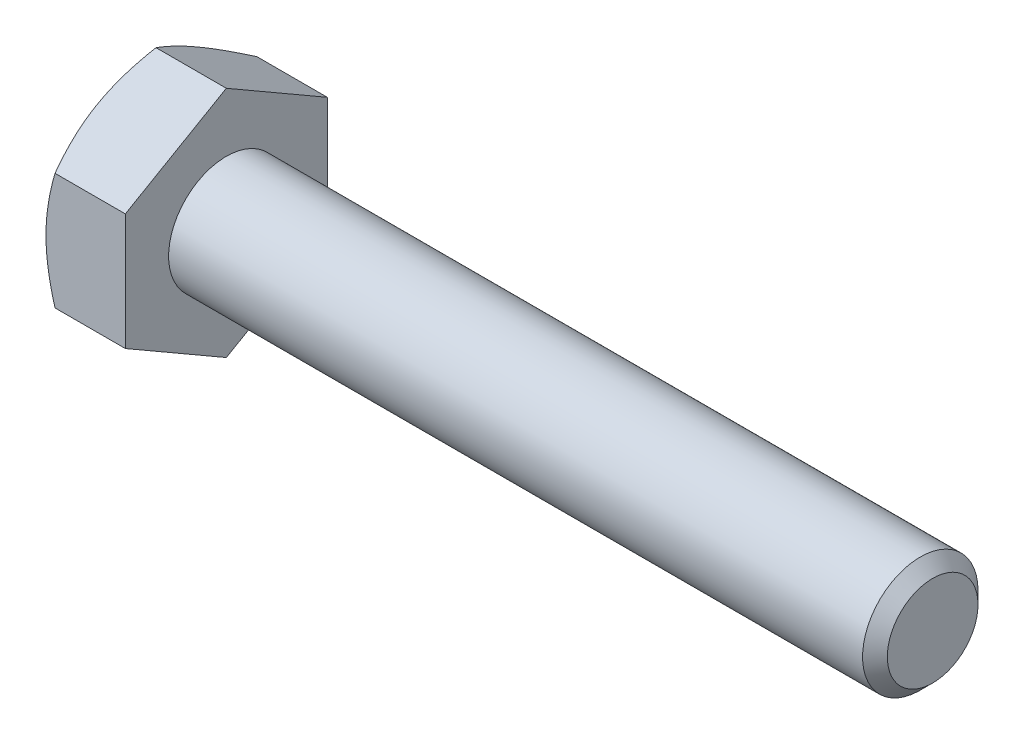
SolidWorks part; units mm, degrees
material "Alloy Steel"
ref_plane "Front Plane" through (0, 0, 0) normal (0, 0, 1) x (1, 0, 0)
ref_plane "Top Plane" through (0, 0, 0) normal (0, 1, 0) x (1, 0, 0)
ref_plane "Right Plane" through (0, 0, 0) normal (1, 0, 0) x (0, 0, -1)
sketch "Sketch1" plane through (0, 0, 0) normal (0, 0, 1) x (1, 0, 0)
  line L0 (-21.6138, 0) -> (21.6138, 0) construction
  line L1 (21.6138, 3.175) -> (21.6138, -3.175) construction
  line L2 (-17.2482, 5.5562) -> (-17.2482, -5.5562) construction
  line L3 (-21.6138, 5.5562) -> (-21.6138, -5.5562) construction
  point P9 (-17.2482, 0)
  point P10 (18.4388, -3.175)
  dimension "Screw Dia" = 6.35
  dimension "Hex" = 11.1125
  dimension "Head Ht" = 4.3656
  dimension "Screw Lenght" = 38.862
  dimension "D1" = 3.175
ref_plane "Plane2" through (21.6138, 0, 0) normal (1, 0, 0) x (0, 0, -1)
sketch "Sketch5" plane through (21.6138, 0, 0) normal (1, 0, 0) x (0, 0, -1)
  circle A0 centre (0, 0) radius 3.175
extrude "Boss-Extrude3" add sketch "Sketch5" against normal up to vertex (38.862 mm away) up to point (-17.2482, 0, 0)
sketch "Sketch9" plane through (21.6138, 0, 0) normal (1, 0, 0) x (0, 0, -1)
  circle A1 centre (0, 0) radius 3.175
  circle A2 centre (0, 0) radius 3.175
  dimension "D1" = 0
curve "Helix/Spiral1" [suppressed] pitch 0.9071 height 19.9571 turns 22 parameters "Pitch"=0.9071
chamfer "Chamfer1" distance 0.6804 angle 45 1 edges at (21.6138, 0, -3.175)
sketch "Sketch10" plane through (0, 0, 0) normal (0, 0, 1) x (1, 0, 0)
  line L0 (21.6138, 3.175) -> (21.954, 2.5858)
  line L1 (21.954, 2.5858) -> (22.0674, 2.5858)
  line L2 (22.0674, 2.5858) -> (22.4076, 3.175)
  line L3 (21.6138, 3.175) -> (22.4076, 3.175)
  line L4 (22.0107, 3.175) -> (22.0107, 2.5858) construction
  line L5 (21.7839, 2.8804) -> (22.2375, 2.8804) construction
  dimension "D1" = 60
  dimension "D2" = 0.1134
  dimension "D3" = 0.4536
sweep "Cut-Sweep1" [suppressed] cut profiles "Sketch10" path "Helix/Spiral1"
sketch "Sketch11" plane through (0, 0, 0) normal (0, 0, 1) x (1, 0, 0)
  line L0 (-17.2482, 3.175) -> (-17.2482, 0)
  line L1 (-17.2482, 0) -> (5.7388, 0)
  line L3 (5.7388, 0) -> (2.5638, 3.175)
  line L4 (-17.2482, 3.175) -> (2.5638, 3.175)
  dimension "D1" = 45
  dimension "MIn Thread" = 19.05
revolve "Revolve1" [suppressed] add sketch "Sketch11" angle 360 about L1
sketch "Sketch6" plane through (-17.2482, 0, 0) normal (-1, 0, 0) x (0, 0, 1)
  line L0 (0, 5.5562) -> (0, -5.5562) construction
  line L1 (5.5562, 3.2079) -> (0, 6.4158)
  line L2 (0, 6.4158) -> (-5.5562, 3.2079)
  line L3 (-5.5562, 3.2079) -> (-5.5562, -3.2079)
  line L4 (-5.5562, -3.2079) -> (0, -6.4158)
  line L5 (0, -6.4158) -> (5.5563, -3.2079)
  line L6 (5.5563, -3.2079) -> (5.5562, 3.2079)
  circle A0 centre (0, 0) radius 5.5562 construction
extrude "Boss-Extrude4" add sketch "Sketch6" along normal up to vertex (4.3656 mm away) up to point (-21.6138, -5.5562, 0)
sketch "Sketch7" plane through (-21.6138, 0, 0) normal (-1, 0, 0) x (0, 0, 1)
  circle A0 centre (0, 0) radius 5.5562 construction
  circle A1 centre (0, 0) radius 5.5562
sketch "Sketch8" plane through (-21.6138, 0, 0) normal (-1, 0, 0) x (0, 0, 1)
  circle A0 centre (0, 0) radius 5.5562 construction
  circle A1 centre (0, 0) radius 5.5562
extrude "Cut-Extrude3" cut sketch "Sketch8" against normal through all draft 60 flip side to cut
sketch "Sketch12" plane through (-21.6138, 0, 0) normal (-1, 0, 0) x (0, 0, 1)
  line L0 (0, 4.2783) -> (0, 2.3892) construction
  line L1 (0.1667, 4.2783) -> (0.1667, 2.3892)
  line L2 (-0.1667, 4.2783) -> (-0.1667, 2.3892)
  line L3 (0, 3.175) -> (0, -3.175) construction
  arc A0 (0.1667, 4.2783) -> (-0.1667, 4.2783) centre (0, 4.2783) ccw
  arc A1 (-0.1667, 2.3892) -> (0.1667, 2.3892) centre (0, 2.3892) ccw
  circle A3 centre (0, 0) radius 2.2225 construction
  circle A4 centre (0, 0) radius 4.445 construction
  point P2 (0, 3.3337)
  dimension "D1" = 4.445
  dimension "D3" = 8.89
  dimension "D2" = 0.3334
extrude "Cut-Extrude4" [suppressed] cut sketch "Sketch12" against normal blind 0.254
pattern_circular "CirPattern1" [suppressed] count 6 over 360 of bodies 116
equation "\"D2@Sketch10\" = \"Pitch@Helix/Spiral1\"*.125"
equation "\"D3@Sketch10\" = \"Pitch@Helix/Spiral1\"*.5"
equation "\"D3@Helix/Spiral1\" = \"MIn Thread@Sketch11\"+\"Pitch@Helix/Spiral1\""
equation "\"D1@Chamfer1\" = \"Pitch@Helix/Spiral1\"*.75"
equation "\"D1@Sketch12\" = \"Hex@Sketch1\"*.4"
equation "\"D3@Sketch12\" = \"Hex@Sketch1\"*.8"
equation "\"D2@Sketch12\" = \"Hex@Sketch1\"*.03"
equation "\"D1@Sketch1\" = \"Pitch@Helix/Spiral1\"*3.5"
